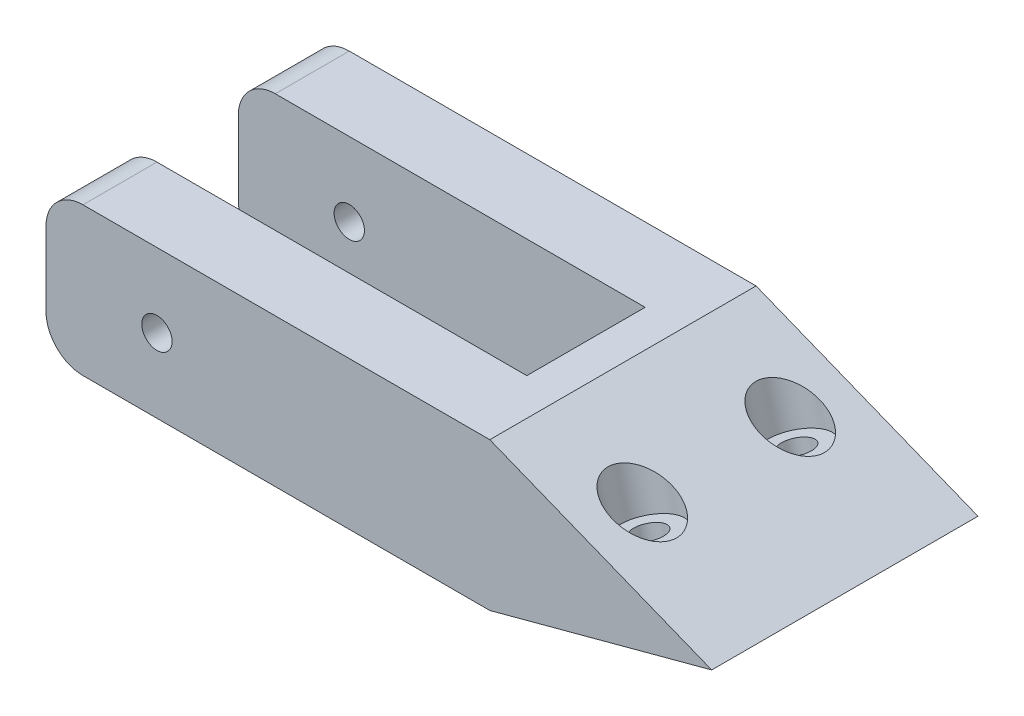
SolidWorks part; units mm, degrees
material "ABS"
ref_plane "Front Plane" through (0, 0, 0) normal (0, 0, 1) x (1, 0, 0)
ref_plane "Top Plane" through (0, 0, 0) normal (0, 1, 0) x (1, 0, 0)
ref_plane "Right Plane" through (0, 0, 0) normal (1, 0, 0) x (0, 0, -1)
other "half_width"
sketch "Sketch4" plane through (0, 0, 0) normal (0, 0, 1) x (1, 0, 0)
  line L0 (-15, 0) -> (40, 0) construction
  line L1 (-10, 10) -> (40, 10)
  line L2 (-15, 5) -> (-15, -5)
  line L3 (-10, -10) -> (40, -10)
  line L4 (40, 10) -> (40, -10)
  line L5 (0, -2.05) -> (0, 2.05) construction
  line L6 (40, 10) -> (45, 10)
  line L7 (40, 10) -> (40, -10)
  line L8 (40, -10) -> (45, -10)
  line L9 (45, 10) -> (45, -10)
  line L10 (45, -10) -> (45, 10)
  line L11 (45, -10) -> (75, -1.9615)
  line L12 (75, -1.9615) -> (45, 10)
  line L13 (45, -10) -> (133.8775, -10) construction
  line L15 (45, 10) -> (40, 10)
  line L16 (45, 10) -> (45, -10)
  line L17 (45, -10) -> (40, -10)
  line L18 (40, 10) -> (40, -10)
  circle A0 centre (0, 0) radius 2.05
  arc A1 (-15, -5) -> (-10, -10) centre (-10, -5) ccw
  arc A2 (-10, 10) -> (-15, 5) centre (-10, 5) ccw
  point P22 (-15, -10)
  point P25 (-15, 10)
  dimension "D8" = 5
  dimension "D1" = 20
  dimension "D2" = 15
  dimension "D3" = 40
  dimension "D4" = 5
  dimension "D5" = 4.1
  dimension "D6" = 15
  dimension "D7" = 30
extrude "Boss-Largeur" add sketch "Sketch4" against normal blind 10 contours L0 L2 L3 L7 | L2 L0 L4 L1 | L9 L6 L4 L7 L8 | A0 | L11 L12 L9 region at (12.9164, 0, 0) region at (42.5, 0, 0) region at (55, -0.6538, 0) region at (0, 0, 0)
extrude "Boss-Extrude4" add sketch "Sketch4<4>" along normal blind 8 contours L9 L6 L4 L8 | L11 L12 L9 region at (42.5, 0, 0) region at (55, -0.6538, 0)
sketch "Sketch4<4>" plane through (0, 0, 0) normal (0, 0, 1) x (1, 0, 0) same geometry as "Sketch4"
sketch "Sketch5" plane through (5.5144, -20.5801, 0) normal (0.2588, -0.9659, 0) x (0.9659, 0.2588, 0)
  line L0 (54.8368, -2) -> (71.9368, -2) construction
  line L1 (56.9368, -2) -> (60.9368, -2) construction
  line L2 (71.9368, -10) -> (71.9368, 8) construction
  line L4 (56.9368, -10) -> (56.9368, -2) construction
  line L5 (40.8785, -10) -> (71.9368, -10) construction
  circle A0 centre (56.9368, -2) radius 2.1
  circle A1 centre (56.9368, -2) radius 4
  point P2 (89.6507, 30.298)
  point P8 (89.7968, 24.6791)
  point P9 (89.7968, 13.1212)
  point P12 (0, 0)
  point P13 (90.6795, 27.62)
  point P14 (0, 0)
  point P15 (89.7968, 42.62)
  point P16 (0, 0)
  point P17 (89.7968, -15)
  dimension "D1" = 8
  dimension "D2" = 2.1
  dimension "D3" = 4
  dimension "D4" = 15
extrude "Cut-Vis" cut sketch "Sketch5" against normal up to next contours A0 | A1 A0 region at (60.5111, -5.8438, -2) region at (56.7567, -6.8498, -2)
extrude "Boss-Vis" add sketch "Sketch5<4>" against normal blind 8
sketch "Sketch5<4>" plane through (5.5144, -20.5801, 0) normal (0.2588, -0.9659, 0) x (0.9659, 0.2588, 0) same geometry as "Sketch5"
ref_plane "Plane1" through (0, 0, 8) normal (0, 0, 1) x (1, 0, 0)
mirror "Mirror4" about plane through (0, 0, 8) normal (0, 0, 1) of bodies 121
extrude "Cut-Extrude7" cut sketch "Sketch4<6>" against normal blind 5 and the other way through all contours A0 region at (0, 0, 0)
sketch "Sketch4<6>" plane through (0, 0, 0) normal (0, 0, 1) x (1, 0, 0) same geometry as "Sketch4"
